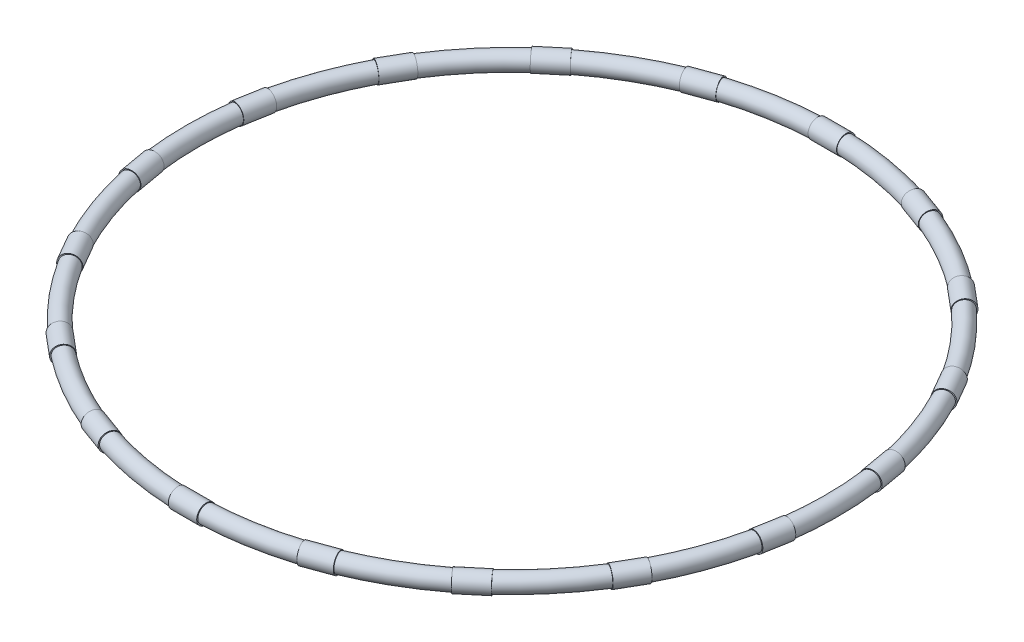
SolidWorks part; units mm, degrees
ref_plane "Plano frontal" through (0, 0, 0) normal (0, 0, 1) x (1, 0, 0)
ref_plane "Plano superior" through (0, 0, 0) normal (0, 1, 0) x (1, 0, 0)
ref_plane "Plano direito" through (0, 0, 0) normal (1, 0, 0) x (0, 0, -1)
sketch "Esboço1" plane through (0, 0, 0) normal (0, 0, 1) x (1, 0, 0)
  line L0 (0, 0) -> (0, 4.7373) construction
  circle A0 centre (22.5, 0) radius 0.62
  dimension "D2" = 1.24
  dimension "D1" = 22.5
revolve "Revolução1" add sketch "Esboço1" angle 360 about L0
sketch "Esboço2" plane through (0, 0, 0) normal (0, 1, 0) x (1, 0, 0)
  line L0 (0, 0) -> (0, 22.5) construction
  line L1 (0, 0) -> (7.6955, 21.1431) construction
  line L2 (0, 0) -> (14.4627, 17.236) construction
  line L3 (0, 0) -> (19.4856, 11.25) construction
  line L4 (0, 0) -> (22.1582, 3.9071) construction
  line L5 (0, 0) -> (22.1582, -3.9071) construction
  line L6 (0, 0) -> (19.4856, -11.25) construction
  line L7 (0, 0) -> (14.4627, -17.236) construction
  line L8 (0, 0) -> (7.6955, -21.1431) construction
  line L9 (0, 0) -> (0, -22.5) construction
  line L10 (0, 0) -> (-7.6955, -21.1431) construction
  line L11 (0, 0) -> (-14.4627, -17.236) construction
  line L12 (0, 0) -> (-19.4856, -11.25) construction
  line L13 (0, 0) -> (-22.1582, -3.9071) construction
  line L14 (0, 0) -> (-22.1582, 3.9071) construction
  line L15 (0, 0) -> (-19.4856, 11.25) construction
  line L16 (0, 0) -> (-14.4627, 17.236) construction
  line L17 (0, 0) -> (-7.6955, 21.1431) construction
  circle A0 centre (0, 0) radius 22.5 construction
  point P24 (0, 0)
  dimension "D1" = 22.5
  dimension "D2" = 18
ref_plane "Plano1" through (1, 0, 0) normal (1, 0, 0) x (0, 0, -1)
sketch "Esboço6" plane through (1, 0, 0) normal (1, 0, 0) x (0, 0, -1)
  line L0 (0, 0) -> (22.5, 0) construction
  line L1 (0, 0) -> (22.5, 0) construction
  circle A0 centre (22.5, 0) radius 0.675
  point P0 (22.5, 0)
  dimension "D1" = 1.35
ref_axis "Eixo1" through (0, -0.715, 0) along (0, 1, 0)
extrude "Ressalto-extrusão1" add sketch "Esboço6" against normal blind 2 separate body
pattern_circular "PadrãoCircular1" count 18 over 360 about axis through (0, -0.715, 0) along (0, 1, 0) of "Ressalto-extrusão1"
